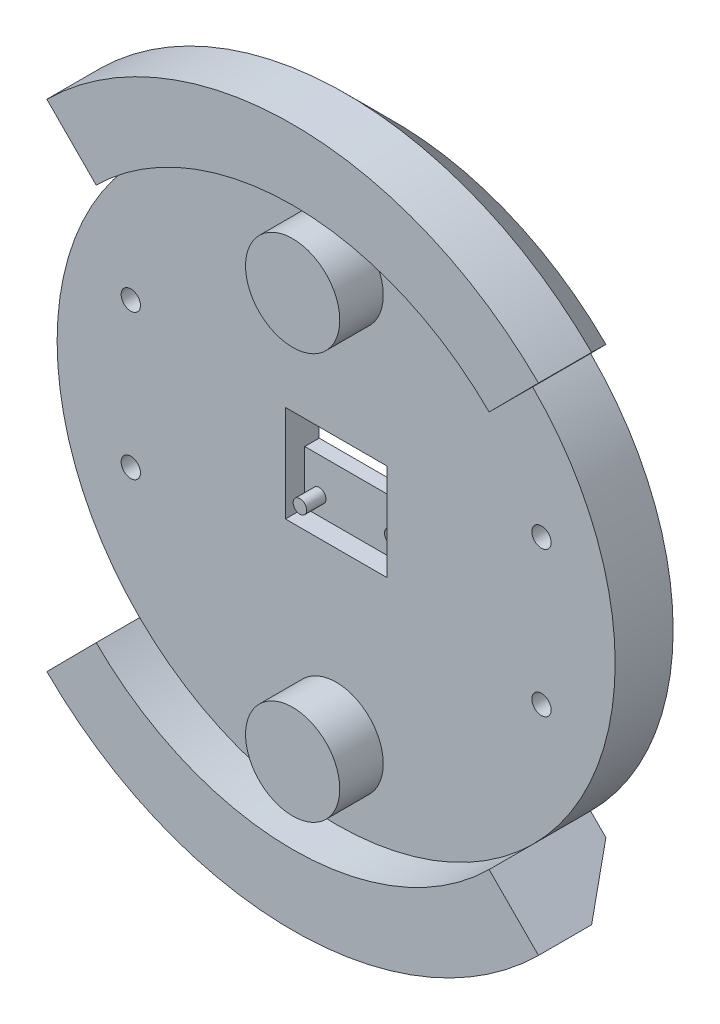
SolidWorks part; units mm, degrees
note: The reader was unsure of these and kept them because the rebuilt part matched: shared geometry of "Sketch1<4>", "Sketch7<6>".
ref_plane "Front Plane" through (0, 0, 0) normal (0, 0, 1) x (1, 0, 0)
ref_plane "Top Plane" through (0, 0, 0) normal (0, 1, 0) x (1, 0, 0)
ref_plane "Right Plane" through (0, 0, 0) normal (1, 0, 0) x (0, 0, -1)
sketch "Sketch1" plane through (0, 0, 0) normal (0, 0, 1) x (1, 0, 0)
  line L0 (-44.2642, 38.0935) -> (-54.5172, 48.3466)
  line L1 (37.2367, -43.7465) -> (47.4471, -54.042)
  line L2 (-44.2642, -43.5773) -> (-54.5172, -53.8304)
  line L3 (37.4066, 38.0935) -> (47.6597, 48.3466)
  line L4 (-3.4288, -74.9919) -> (-3.4288, -60.4919) construction
  line L5 (-44.0943, -43.7465) -> (-54.3047, -54.042)
  line L6 (47.6597, -53.8304) -> (37.4066, -43.5773)
  line L7 (-44.0943, 38.2627) -> (-54.3047, 48.5583)
  line L8 (47.4471, 48.5583) -> (37.2367, 38.2627)
  circle A0 centre (-3.4288, -2.7419) radius 57.75
  circle A1 centre (-3.4288, -2.7419) radius 72.25
  dimension "D1" = 144.5
  dimension "D2" = 115.5
  dimension "D3" = 45
  dimension "D4" = 90
  dimension "D5" = 90
  dimension "D6" = 45
  dimension "D7" = 0.3
  dimension "D8" = 0.3
  dimension "D9" = 0.3
  dimension "D10" = 0.3
extrude "Boss-Extrude2" add sketch "Sketch1" along normal blind 12 contours A0 L0
extrude "Boss-Extrude3" add sketch "Sketch1<4>" along normal blind 21 contours L3 A1 L0 A0 | L2 A1 L1 A0 | A1 L4 A0 L2
sketch "Sketch1<4>" plane through (0, 0, 0) normal (0, 0, 1) x (1, 0, 0) same geometry as "Sketch1"
sketch "Sketch2" plane through (0, 0, 0) normal (0, 0, -1) x (-1, 0, 0)
  line L1 (53.9288, 22.7581) -> (-47.0712, 22.7581)
  line L2 (53.9288, 22.7581) -> (53.9288, -28.2419)
  line L3 (53.9288, -28.2419) -> (-47.0712, -28.2419)
  line L4 (-47.0712, 22.7581) -> (-47.0712, -28.2419)
  circle A0 centre (3.4288, -2.7419) radius 57.5 construction
  dimension "D3" = 50.5
  dimension "D4" = 25.5
  dimension "D1" = 101
  dimension "D2" = 51
extrude "Cut-Extrude1" cut sketch "Sketch2" against normal blind 5
sketch "Sketch4" plane through (0, 0, 5) normal (0, 0, -1) x (-1, 0, 0)
  line L0 (-7.0712, -10.9919) -> (13.9288, -10.9919)
  line L1 (-7.0712, -10.9919) -> (-7.0712, 9.0081)
  line L2 (-7.0712, 9.0081) -> (13.9288, 9.0081)
  line L3 (13.9288, -10.9919) -> (13.9288, 9.0081)
  arc A1 (44.0943, -43.7465) -> (44.0943, 38.2627) centre (3.4288, -2.7419) ccw construction
  arc A2 (-37.2367, 38.2627) -> (-37.2367, -43.7465) centre (3.4288, -2.7419) ccw construction
  dimension "D1" = 21
  dimension "D2" = 20
  dimension "D3" = 8.25
  dimension "D4" = 10.5
extrude "Cut-Extrude2" cut sketch "Sketch4" against normal blind 8
sketch "Sketch5" plane through (0, 0, 5) normal (0, 0, -1) x (-1, 0, 0)
  line L0 (13.9288, -10.9919) -> (13.9288, 9.0081) construction
  line L1 (-7.0712, -10.9919) -> (13.9288, -10.9919)
  line L2 (-7.0712, -10.9919) -> (-7.0712, 29.8182)
  line L3 (-7.0712, 29.8182) -> (13.9288, 29.8182)
  line L4 (13.9288, -10.9919) -> (13.9288, 29.8182)
extrude "Cut-Extrude3" cut sketch "Sketch5" against normal blind 3 and the other way blind 35
sketch "Sketch6" plane through (0, 0, 5) normal (0, 0, -1) x (-1, 0, 0)
  line L0 (-7.0712, 22.7581) -> (-7.0712, -10.9919) construction
  line L1 (13.9288, -10.9919) -> (-7.0712, -10.9919)
  line L2 (13.9288, -10.9919) -> (13.9288, 0)
  line L3 (13.9288, 0) -> (-7.0712, 0)
  line L4 (-7.0712, -10.9919) -> (-7.0712, 0)
  line L6 (-7.0712, -10.9919) -> (13.9288, -10.9919) construction
  line L7 (13.9288, -10.9919) -> (13.9288, 22.7581) construction
extrude "Boss-Extrude4" add sketch "Sketch6" against normal blind 3
sketch "Sketch7" plane through (0, 0, 5) normal (0, 0, -1) x (-1, 0, 0)
  line L0 (-7.0712, -10.9919) -> (13.9288, -10.9919) construction
  line L2 (-7.0712, -10.9919) -> (-7.0712, 9.0081) construction
  circle A0 centre (-4.0712, -7.2419) radius 1.5
  circle A1 centre (10.9288, -7.2419) radius 1.4
  dimension "D1" = 15
  dimension "D2" = 3
  dimension "D3" = 2.8
  dimension "D4" = 3.75
  dimension "D5" = 3
sketch "Sketch9" plane through (0, 0, 12) normal (0, 0, 1) x (1, 0, 0)
  circle A0 centre (-45.9288, -17.7419) radius 2
  circle A1 centre (-45.9288, 12.2581) radius 2
  circle A2 centre (39.0712, 12.2581) radius 2
  circle A3 centre (39.0712, -17.7419) radius 2
  circle A4 centre (-3.4288, -2.7419) radius 57.5 construction
  dimension "D1" = 85
  dimension "D3" = 42.5
  dimension "D4" = 15
  dimension "D5" = 4
  dimension "D2" = 30
extrude "Cut-Extrude6" cut sketch "Sketch9" against normal blind 31
sketch "Sketch12" plane through (0, 0, 12) normal (0, 0, 1) x (1, 0, 0)
  line L0 (-3.4288, -60.4919) -> (-3.4288, 55.0081) construction
  circle A0 centre (-3.4288, -44.7419) radius 9.75
  circle A1 centre (-3.4288, 39.2581) radius 9.75
  circle A2 centre (-3.4288, -2.7419) radius 57.75 construction
  arc A3 (-44.0943, 38.2627) -> (-44.0943, -43.7465) centre (-3.4288, -2.7419) ccw construction
  dimension "D1" = 19.5
  dimension "D2" = 42
  dimension "D3" = 42
extrude "Boss-Extrude5" add sketch "Sketch12" along normal blind 9
extrude "Boss-Extrude6" add sketch "Sketch7" against normal up to vertex (7 mm away) contours A1
extrude "Cut-Extrude10" cut sketch "Sketch7<6>" against normal blind 10 contours A0
sketch "Sketch7<6>" plane through (0, 0, 5) normal (0, 0, -1) x (-1, 0, 0) same geometry as "Sketch7"
chamfer "Chamfer1" distance 10 angle 45 2 edges at (-3.4288, -74.9919, 0) (-3.4288, 69.5081, 0)
